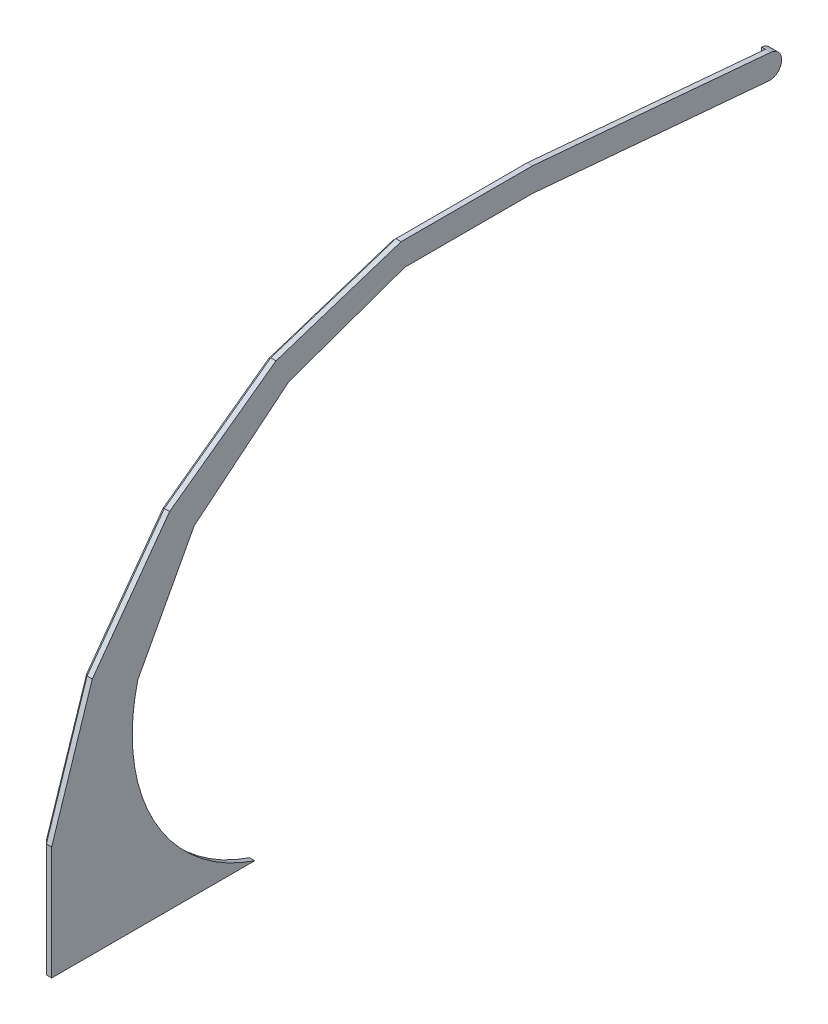
SolidWorks part; units mm, degrees
ref_plane "Front Plane" through (0, 0, 0) normal (0, 0, 1) x (1, 0, 0)
ref_plane "Top Plane" through (0, 0, 0) normal (0, 1, 0) x (1, 0, 0)
ref_plane "Right Plane" through (0, 0, 0) normal (1, 0, 0) x (0, 0, -1)
sketch "Sketch1" plane through (0, 0, 0) normal (1, 0, 0) x (0, 0, -1)
  line L0 (12.6153, -92.6333) -> (182.6153, -92.6333)
  line L6 (415.1195, 274.7215) -> (612.6153, 257.4428)
  line L8 (614.3584, 277.3667) -> (415.1195, 294.7979)
  line L9 (12.6153, -92.6333) -> (12.6153, 2.3615)
  line L10 (12.6153, 2.3615) -> (46.6281, 107.0421)
  line L11 (46.6281, 107.0421) -> (111.3243, 196.0888)
  line L12 (111.3243, 196.0888) -> (200.371, 260.7851)
  line L13 (200.371, 260.7851) -> (305.0517, 294.7979)
  line L14 (305.0517, 294.7979) -> (415.1195, 294.7979)
  line L15 (452.6153, 271.441) -> (183.2145, -92.6333) construction
  line L16 (452.6153, 271.441) -> (634.136, -92.6333) construction
  line L20 (84.8259, 87.5794) -> (131.9298, 175.4834)
  line L21 (131.9298, 175.4834) -> (210.8849, 240.1505)
  line L22 (210.8849, 240.1505) -> (308.2365, 274.69)
  line L23 (308.2365, 274.69) -> (415.1195, 274.7215)
  line L24 (111.3243, 196.0888) -> (131.9298, 175.4834) construction
  line L25 (200.371, 260.7851) -> (210.8849, 240.1505) construction
  line L26 (46.6281, 107.0421) -> (84.8259, 87.5794) construction
  line L27 (183.2145, -92.6333) -> (634.136, -92.6333) construction
  line L28 (305.0517, 294.7979) -> (308.2365, 274.69) construction
  arc A0 (84.8259, 87.5794) -> (182.6153, -92.6333) centre (230.5143, 49.9965) ccw
  arc A2 (612.6153, 257.4428) -> (614.3584, 277.3667) centre (613.4869, 267.4048) ccw
  dimension "D1" = 600
  dimension "D2" = 200
  dimension "D3" = 5
  dimension "D4" = 370
  dimension "D5" = 20
  dimension "D12" = 162
  dimension "D13" = 162
  dimension "D14" = 162
  dimension "D15" = 162
  dimension "D16" = 170
  dimension "D18" = 63
  dimension "D19" = 58.5
  dimension "D20" = 160
  dimension "D6" = 81
  dimension "D7" = 81
  dimension "D8" = 81
  dimension "D17" = 162
  dimension "D21" = 81
extrude "Boss-Extrude1" add sketch "Sketch1" against normal blind 4.4
sketch "Sketch2" plane through (-4.4, 0, 0) normal (-1, 0, 0) x (0, 0, 1)
  line L0 (-614.3584, 277.3667) -> (-614.0795, 274.1789)
  line L1 (-614.0795, 274.1789) -> (-415.1195, 291.5856)
  line L2 (-612.8942, 260.6306) -> (-415.1195, 277.9337)
  line L3 (-612.8942, 260.6306) -> (-612.6153, 257.4428)
  line L4 (-415.1195, 294.7979) -> (-415.1195, 274.7215) construction
  line L5 (-305.0517, 294.7979) -> (-308.2365, 274.69) construction
  line L6 (-200.371, 260.7851) -> (-210.8849, 240.1505) construction
  line L7 (-415.1195, 291.5856) -> (-305.5605, 291.5856)
  line L8 (-415.1195, 277.9337) -> (-307.7277, 277.902)
  line L9 (-307.7277, 277.902) -> (-209.4209, 243.0237)
  line L10 (-305.5605, 291.5856) -> (-201.8475, 257.8873)
  line L11 (-111.3243, 196.0888) -> (-131.9298, 175.4834) construction
  line L12 (-46.6281, 107.0421) -> (-84.8259, 87.5794) construction
  line L13 (-12.6153, 2.3615) -> (4.5632, 2.3604) construction
  line L14 (-201.8475, 257.8873) -> (-113.624, 193.7891)
  line L15 (-113.624, 193.7891) -> (-49.5259, 105.5656)
  line L16 (-49.5259, 105.5656) -> (-15.9929, 2.3617)
  line L17 (-15.9929, 2.3617) -> (-15.9929, -92.6333)
  line L18 (-12.6153, -92.6333) -> (-182.6153, -92.6333) construction
  line L19 (-15.9929, -92.6333) -> (-101.9058, -92.6333)
  line L20 (-101.9058, -92.6333) -> (-66.3503, 2.3647)
  line L21 (-66.3503, 2.3647) -> (-82.1251, 88.9555)
  line L22 (-82.1251, 88.9555) -> (-129.6911, 177.722)
  line L23 (-129.6911, 177.722) -> (-209.4209, 243.0237)
  line L26 (-415.1195, 294.7979) -> (-305.0517, 294.7979) construction
  line L27 (-308.2365, 274.69) -> (-415.1195, 274.7215) construction
  line L28 (-614.3584, 277.3667) -> (-415.1195, 294.7979) construction
  line L29 (-415.1195, 274.7215) -> (-612.6153, 257.4428) construction
  line L30 (-305.0517, 294.7979) -> (-200.371, 260.7851) construction
  line L31 (-210.8849, 240.1505) -> (-308.2365, 274.69) construction
  line L32 (-200.371, 260.7851) -> (-111.3243, 196.0888) construction
  line L33 (-131.9298, 175.4834) -> (-210.8849, 240.1505) construction
  line L34 (-111.3243, 196.0888) -> (-46.6281, 107.0421) construction
  line L35 (-84.8259, 87.5794) -> (-131.9298, 175.4834) construction
  line L36 (-46.6281, 107.0421) -> (-12.6153, 2.3615) construction
  line L37 (-12.6153, 2.3615) -> (-12.6153, -92.6333) construction
  line L39 (-573.6826, 271.3891) -> (-562.7245, 272.3478)
  line L40 (-573.6826, 271.3891) -> (-573.3166, 267.2051)
  line L41 (-573.3166, 267.2051) -> (-562.3584, 268.1638)
  line L42 (-562.7245, 272.3478) -> (-562.3584, 268.1638)
  line L43 (-522.8767, 275.834) -> (-511.9186, 276.7928)
  line L44 (-522.8767, 275.834) -> (-522.5107, 271.65)
  line L45 (-522.5107, 271.65) -> (-511.5525, 272.6087)
  line L46 (-511.9186, 276.7928) -> (-511.5525, 272.6087)
  line L47 (-619.1489, 269.0174) -> (-608.1908, 269.9761)
  line L48 (-619.1489, 269.0174) -> (-618.7829, 264.8334)
  line L49 (-618.7829, 264.8334) -> (-607.8248, 265.7921)
  line L50 (-608.1908, 269.9761) -> (-607.8248, 265.7921)
  arc A0 (-614.3584, 277.3667) -> (-612.6153, 257.4428) centre (-613.4869, 267.4048) ccw
  dimension "D1" = 3.2
  dimension "D2" = 3.2
  dimension "D3" = 4.2
  dimension "D4" = 11
  dimension "D5" = 40
  dimension "D6" = 4.2
  dimension "D7" = 11
  dimension "D8" = 40
  dimension "D9" = 9.5
  dimension "D10" = 9.5
  dimension "D11" = 11
  dimension "D12" = 5.5
  dimension "D13" = 4.2
  dimension "D14" = 2.1
extrude "Boss-Extrude2" add sketch "Sketch2" along normal blind 3.2
equation "\"Phone height\"= 370"
equation "\"edge distance from wall\"= 600"
equation "\"phone angle\"= 5"
equation "\"D1@Sketch1\"=\"edge distance from wall\""
equation "\"base depth\"= 170"
equation "\"width\"= 108"
equation "\"Phone segment length\"= 200"
equation "\"D2@Sketch1\"=\"Phone segment length\""
equation "\"D3@Sketch1\"=\"phone angle\""
equation "\"D4@Sketch1\"=\"Phone height\""
equation "\"Phone segment thick\"= 20"
equation "\"D5@Sketch1\"=\"Phone segment thick\""
equation "\"Phone segment acute angle\"= 1"
equation "\"D16@Sketch1\"=\"base depth\""
equation "\"upper segment count\"= 6"
equation "\"lower segment count\"= 5"
equation "\"upper segment angle\"= 180 - ( 90 / ( \"upper segment count\" - 1 ) )"
equation "\"D12@Sketch1\"=\"upper segment angle\""
equation "\"D13@Sketch1\"=\"upper segment angle\""
equation "\"D14@Sketch1\"=\"upper segment angle\""
equation "\"D15@Sketch1\"=\"upper segment angle\""
equation "\"lower segment angle\"= 180 - ( 90 / ( \"lower segment count\" - 1 ) )"
equation "\"fov\"=63"
equation "\"D18@Sketch1\"=\"fov\""
equation "\"D19@Sketch1\"=(180-\"fov\")/2"
equation "\"D6@Sketch1\"=\"upper segment angle\"/2"
equation "\"D7@Sketch1\"=\"upper segment angle\"/2"
equation "\"D8@Sketch1\"=\"upper segment angle\"/2"
equation "\"D17@Sketch1\"=\"upper segment angle\""
equation "\"D21@Sketch1\"=\"upper segment angle\"/2"
equation "\"Thicker acrylic\"= 4.4"
equation "\"Thinner acrylic\"= 3.2"
equation "\"D1@Boss-Extrude1\"=\"Thicker acrylic\""
equation "\"D1@Sketch2\"=\"Thinner acrylic\""
equation "\"D2@Sketch2\"=\"Thinner acrylic\""
equation "\"phone thick\"= 9.5"
equation "\"phone support width\"= 10"
equation "\"fit\"= 1"
equation "\"D3@Sketch2\"=\"Thinner acrylic\"+\"fit\""
equation "\"D4@Sketch2\"=\"phone support width\"+\"fit\""
equation "\"D5@Sketch2\"=40"
equation "\"D6@Sketch2\"=\"Thinner acrylic\"+\"fit\""
equation "\"D7@Sketch2\"=\"phone support width\"+\"fit\""
equation "\"D9@Sketch2\"=\"phone thick\""
equation "\"D10@Sketch2\"=\"phone thick\""
equation "\"D1@Boss-Extrude2\"=\"Thinner acrylic\""
equation "\"D11@Sketch2\"=\"phone support width\"+\"fit\""
equation "\"D12@Sketch2\"=\"D11@Sketch2\"/2"
equation "\"D13@Sketch2\"=\"Thinner acrylic\"+\"fit\""
equation "\"D14@Sketch2\"=\"D13@Sketch2\"/2"
equation "\"phone support length\"= 98.5"
